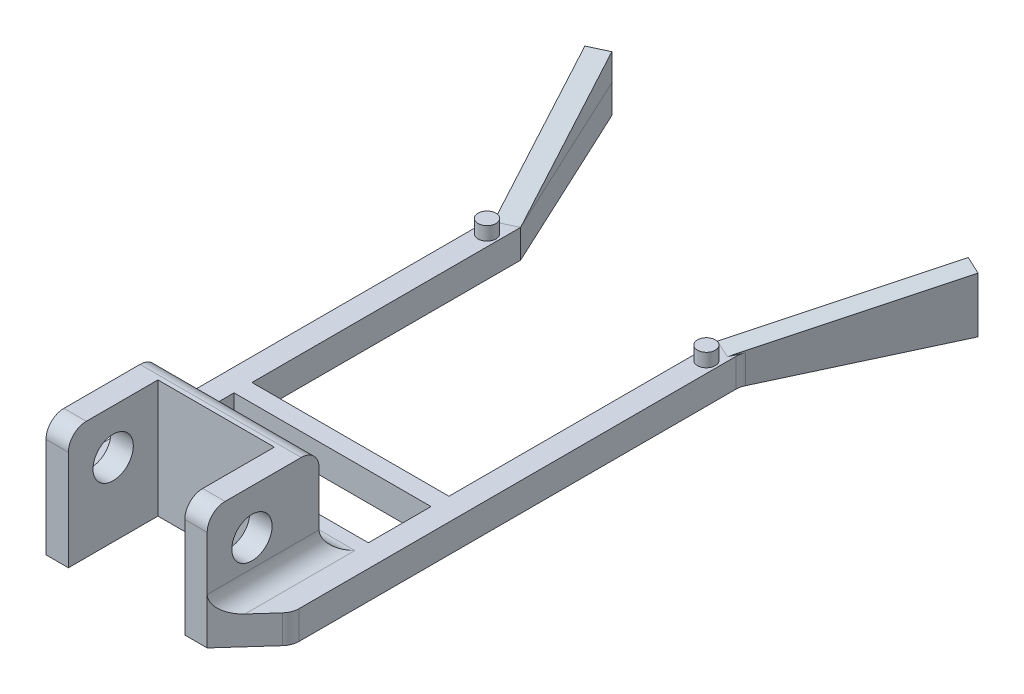
SolidWorks part; units mm, degrees
ref_plane "Front Plane" through (0, 0, 0) normal (0, 0, 1) x (1, 0, 0)
ref_plane "Top Plane" through (0, 0, 0) normal (0, 1, 0) x (1, 0, 0)
ref_plane "Right Plane" through (0, 0, 0) normal (1, 0, 0) x (0, 0, -1)
sketch "Sketch1" plane through (0, 0, 0) normal (0, 1, 0) x (1, 0, 0)
  line L0 (0, -55) -> (0, 55) construction
  line L12 (11, 0) -> (11, 30)
  line L15 (-11, 0) -> (-11, 30)
  line L16 (-11, 0) -> (11, 0)
  line L17 (-13.5, 30) -> (-13.5, -20)
  line L18 (13.5, -20) -> (13.5, 30)
  line L19 (-11, 30) -> (-19.8989, 49.0837)
  line L20 (-19.8989, 49.0837) -> (-21.9524, 48.1262)
  line L21 (-21.9524, 48.1262) -> (-13.5, 30)
  line L22 (19.8989, 49.0837) -> (21.9524, 48.1262)
  line L23 (21.9524, 48.1262) -> (13.5, 30)
  line L24 (11, 30) -> (19.8989, 49.0837)
  line L25 (6.5, -15) -> (6.5, -25)
  line L26 (6.5, -25) -> (9, -25)
  line L29 (-6.5, -15) -> (-6.5, -25)
  line L30 (-6.5, -25) -> (-9, -25)
  line L32 (-6.5, -15) -> (6.5, -15)
  line L33 (9, -25) -> (13.5, -20)
  line L34 (-13.5, -20) -> (-9, -25)
  line L36 (-11, -2) -> (11, -2)
  line L37 (-11, -2) -> (-11, -9)
  line L38 (-11, -9) -> (11, -9)
  line L39 (11, -2) -> (11, -9)
  point P0 (0, 0)
  point P23 (6.5, -20)
  point P27 (0, 0)
  point P28 (0, 0)
  dimension "D1" = 22
  dimension "D2" = 13
  dimension "D3" = 2.5
  dimension "D4" = 20
  dimension "D5" = 155
  dimension "D6" = 55
  dimension "D7" = 2.5
  dimension "D8" = 10
  dimension "D9" = 15
  dimension "D10" = 2
  dimension "D11" = 6
extrude "Boss-Extrude1" add sketch "Sketch1" along normal blind 3.175
sketch "Sketch5" plane through (0, 3.175, 0) normal (0, 1, 0) x (1, 0, 0)
  line L1 (11, 30) -> (13.5, 30) construction
  line L2 (11, 30) -> (11, 0) construction
  line L3 (13.5, -20) -> (13.5, 30) construction
  circle A0 centre (12.25, 27.5) radius 1
  point P8 (12.25, 30)
  dimension "D1" = 2
  dimension "D2" = 2.5
extrude "Boss-Extrude4" add sketch "Sketch5" along normal blind 1.5
sketch "Sketch2" plane through (2.4553, 0, -1.1449) normal (0.9063, 0, -0.4226) x (-0.4226, 0, -0.9063)
  line L0 (31.838, 3.175) -> (52.8946, 6.175)
  line L1 (52.8946, 6.175) -> (52.8946, 3.175)
  line L2 (31.838, 3.175) -> (52.8946, 3.175) construction
  line L3 (31.838, 3.175) -> (52.8946, 3.175)
  dimension "D1" = 3
extrude "Boss-Extrude2" add sketch "Sketch2" against normal up to surface (2.2658 mm away) separate body up to face at (-17.7262, 1.5875, -39.0631)
mirror "Mirror4" about plane through (0, 0, 0) normal (1, 0, 0) of "Boss-Extrude4", "Boss-Extrude2"
sketch "Sketch3" plane through (0, 3.175, 0) normal (0, 1, 0) x (1, 0, 0)
  line L0 (-6.5, -15) -> (6.5, -15) construction
  line L7 (-6.5, -15) -> (6.5, -15)
  line L9 (-9, -15) -> (-9, -12.5)
  line L11 (-9, -12.5) -> (9, -12.5)
  line L22 (9, -15) -> (9, -12.5)
  line L23 (6.5, -25) -> (9, -25) construction
  line L24 (9, -25) -> (6.5, -25)
  line L25 (9, -25) -> (9, -15)
  line L27 (6.5, -25) -> (6.5, -15)
  line L28 (6.5, -15) -> (6.5, -25) construction
  line L29 (0, -55) -> (0, 55) construction
  line L31 (-6.5, -25) -> (-6.5, -15)
  line L32 (-9, -25) -> (-6.5, -25)
  line L33 (-9, -25) -> (-9, -15)
  line L34 (-13.5, -20) -> (-9, -25) construction
  line L35 (-9, -25) -> (-6.5, -25) construction
extrude "Boss-Extrude3" add sketch "Sketch3" along normal blind 10
sketch "Sketch4" plane through (9, 0, 0) normal (1, 0, 0) x (0, 0, -1)
  line L2 (-25, 13.175) -> (-25, 3.175) construction
  line L3 (-15, 3.175) -> (-25, 3.175) construction
  circle A0 centre (-20, 8.175) radius 2.25
  point P11 (-25, 8.175)
  point P12 (-20, 3.175)
  dimension "D1" = 4.5
extrude "Cut-Extrude1" cut sketch "Sketch4" against normal through all
fillet "Fillet1" radius 2 10 edges at (-9, 3.175, 18.75) (9, 3.175, 18.75) (13.5, 1.5875, -30) (13.5, 1.5875, 20) (-13.5, 1.5875, -30) (-13.5, 1.5875, 20) (7.75, 13.175, 25) (-7.75, 13.175, 25) (0, 13.175, 12.5) (0, 3.175, 12.5)
